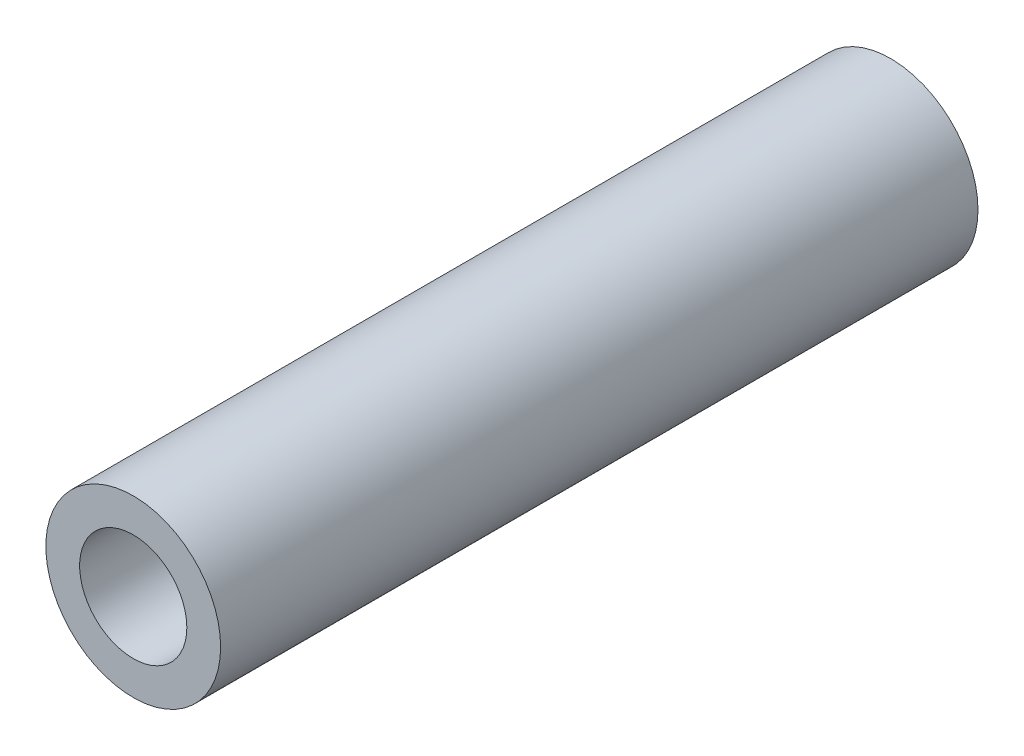
SolidWorks part; units mm, degrees
material "Nylon 6/10"
ref_plane "Front Plane" through (0, 0, 0) normal (0, 0, 1) x (1, 0, 0)
ref_plane "Top Plane" through (0, 0, 0) normal (0, 1, 0) x (1, 0, 0)
ref_plane "Right Plane" through (0, 0, 0) normal (1, 0, 0) x (0, 0, -1)
sketch "Sketch1" plane through (0, 0, 0) normal (0, 0, 1) x (1, 0, 0)
  circle A0 centre (0, 0) radius 2.3813
  circle A1 centre (0, 0) radius 1.4605
  dimension "OD" = 4.7625
  dimension "ID" = 2.921
extrude "Extrude1" add sketch "Sketch1" along normal mid plane 20.6375
sketch "Sketch2" plane through (0, 0, 0) normal (1, 0, 0) x (0, 0, -1)
  line L0 (-10.3187, -1.4605) -> (10.3187, -1.4605) construction
  line L3 (10.3187, 1.4605) -> (-10.3187, 1.4605) construction
  line L5 (-10.3187, -1.4605) -> (10.3187, -1.4605)
  line L6 (10.3187, 1.4605) -> (-10.3187, 1.4605)
sketch "Sketch4" plane through (0, 0, 10.3187) normal (0, 0, 1) x (1, 0, 0)
  line L0 (0, 0) -> (-1.0327, 1.0327)
  line L1 (0, -2.6194) -> (0, 2.6194) construction
  circle A0 centre (0, 0) radius 1.4605 construction
  dimension "D1" = 45
